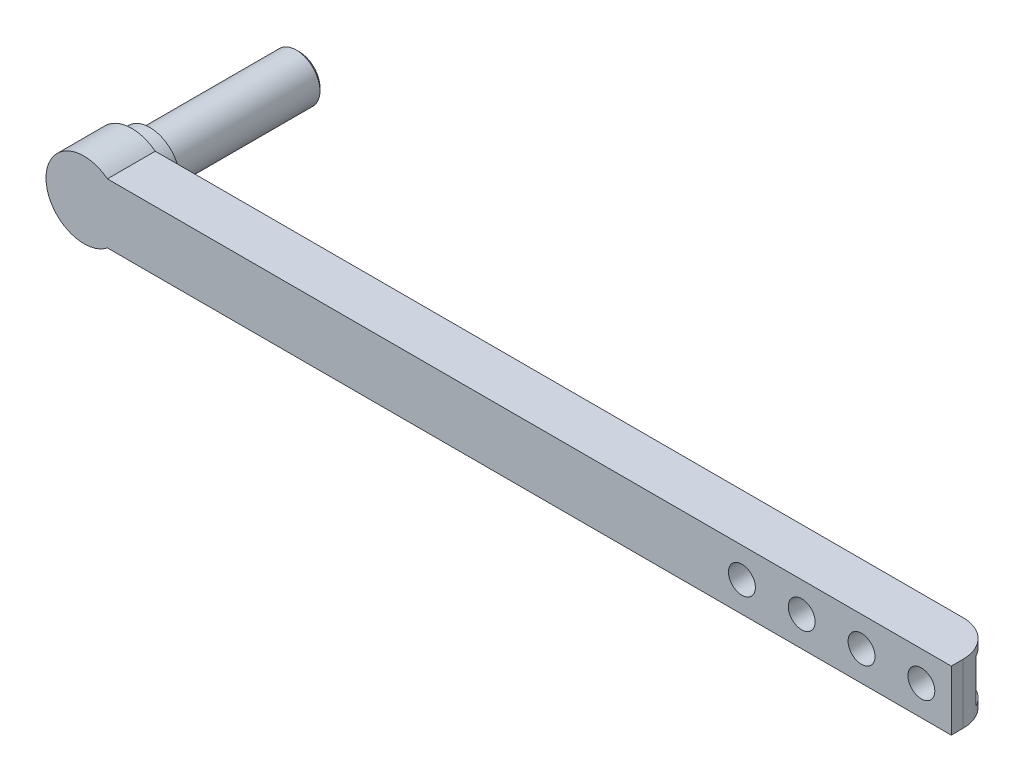
SolidWorks part; units mm, degrees
ref_plane "Front Plane" through (0, 0, 0) normal (0, 0, 1) x (1, 0, 0)
ref_plane "Top Plane" through (0, 0, 0) normal (0, 1, 0) x (1, 0, 0)
ref_plane "Right Plane" through (0, 0, 0) normal (1, 0, 0) x (0, 0, -1)
sketch "Sketch1" plane through (0, 0, 0) normal (0, 0, 1) x (1, 0, 0)
  circle A0 centre (0, 0) radius 3.95
  dimension "D1" = 7.9
extrude "Boss-Extrude1" add sketch "Sketch1" against normal blind 28
sketch "Sketch2" plane through (0, 0, 0) normal (0, 0, 1) x (1, 0, 0)
  line L0 (0, 0) -> (145, 0) construction
  line L2 (145, 5) -> (0, 5)
  line L3 (145, 5) -> (145, -5)
  line L4 (145, -5) -> (0, -5)
  line L5 (0, 5) -> (0, -5)
  line L6 (72.5, -5) -> (72.5, 5) construction
  line L7 (145, 0) -> (0, 0) construction
  circle A0 centre (0, 0) radius 6.35
  point P275 (72.5, 0)
  circle M7 centre (0, 0) radius 3.95
  dimension "D3" = 12.7
  dimension "D1" = 145
  dimension "D2" = 10
extrude "Boss-Extrude2" add sketch "Sketch2" along normal blind 8 contours L2 A0 L4 L5 M7 | L4 A0 L2 L5 M7 | A0 L4 L3 L2 | L5 M7 | L5 M7 region at (75.3046, 0, 0) region at (5.6022, 2.729, 0) region at (1.9572, 5.1633, 0) region at (1.6764, 0, 0) region at (-1.6764, 0, 0)
sketch "Sketch3" plane through (0, 0, 0) normal (0, 0, 1) x (1, 0, 0)
  circle A0 centre (0, 0) radius 5
  dimension "D1" = 10
extrude "Boss-Extrude3" add sketch "Sketch3" against normal blind 3
sketch "Sketch4" plane through (0, 0, 8) normal (0, 0, 1) x (1, 0, 0)
  line L0 (0, 0) -> (-21.0956, 0) construction
  line L1 (0, 0) -> (10.5478, 18.2693) construction
  line L2 (-6.35, -1.66) -> (-15.3278, -1.66)
  line L3 (-6.35, -1.66) -> (-6.35, 1.66)
  line L4 (-6.35, 1.66) -> (-15.3278, 1.66)
  line L5 (-15.3278, -1.66) -> (-15.3278, 1.66)
  line L6 (-10.8389, 1.66) -> (-10.8389, -1.66) construction
  line L7 (-6.35, 0) -> (-15.3278, 0) construction
  line L8 (1.7374, 6.3292) -> (4.6126, 4.6693)
  line L9 (1.7374, 6.3292) -> (6.2263, 14.1042)
  line L10 (6.2263, 14.1042) -> (9.1015, 12.4443)
  line L11 (4.6126, 4.6693) -> (9.1015, 12.4443)
  line L12 (0, 0) -> (10.5478, -18.2693) construction
  line L13 (4.6126, -4.6693) -> (1.7374, -6.3292)
  line L14 (4.6126, -4.6693) -> (9.1015, -12.4443)
  line L15 (9.1015, -12.4443) -> (6.2263, -14.1042)
  line L16 (1.7374, -6.3292) -> (6.2263, -14.1042)
  arc A0 (3.9144, 5) -> (3.9144, -5) centre (0, 0) ccw construction
  point P4 (-10.8389, 0)
  point P24 (0, 0)
sketch "Sketch5" plane through (145, 0, 0) normal (1, 0, 0) x (0, 0, -1)
  line L0 (0, 5) -> (0, -5) construction
  line L1 (0, 3.625) -> (-3.2, 3.625)
  line L2 (0, 3.625) -> (0, -3.625)
  line L3 (0, -3.625) -> (-3.2, -3.625)
  line L4 (-3.2, 3.625) -> (-3.2, -3.625)
  line L5 (-1.6, -3.625) -> (-1.6, 3.625) construction
  line L6 (0, 0) -> (-3.2, 0) construction
  line L7 (0, 0) -> (-8, 0) construction
  line L8 (-8, 5) -> (-8, -5) construction
  point P264 (-1.6, 0)
  dimension "D1" = 4.8
  dimension "D2" = 7.25
extrude "Cut-Extrude1" cut sketch "Sketch5" against normal blind 42
hole_wizard "M4 Clearance Hole1" positions "Sketch6" profile "Sketch7" hole size "M4" standard "ANSI Metric" end condition through all
sketch "Sketch6" plane through (0, 0, 8) normal (0, 0, 1) x (1, 0, 0)
  line L0 (110, 0) -> (120, 0) construction
  line L1 (120, 0) -> (130, 0) construction
  line L2 (130, 0) -> (140, 0) construction
  line L3 (140, 0) -> (145, 0) construction
  line L4 (145, 5) -> (145, -5) construction
  point P0 (140, 0)
  point P2 (130, 0)
  point P4 (120, 0)
  point P6 (110, 0)
  dimension "D1" = 5
  dimension "D2" = 10
sketch "Sketch7" plane through (140, 0, 8) normal (1, 0, 0) x (0, -1, 0)
  line L0 (0, 0) -> (0, 36)
  line L1 (0, 36) -> (2.25, 36)
  line L2 (2.25, 36) -> (2.25, 0)
  line L5 (2.25, 0) -> (0, 0)
  line L11 (0, -6.35) -> (0, 107.95) construction
  dimension "Thru Hole Dia." = 4.5
  dimension "Thru Hole Depth" = 36
chamfer "Chamfer1" distance 0.5 angle 45 1 edges at (3.95, 0, -28)
fillet "Fillet1" radius 3.7 2 edges at (103, -3.625, 1.6) (103, 3.625, 1.6)
fillet "Fillet5" radius 6 2 edges at (145, -4.3125, 0) (145, 4.3125, 0) tangent propagation no
ref_plane "Plane1" [suppressed] through (5, 0, 0) normal (1, 0, 0) x (0, 0, -1)
split "Split1" [suppressed] bodies to split 106 resulting bodies 107 108
delete or keep bodies "Body-Delete/Keep 1" [suppressed] type keep bodies bodies 107
